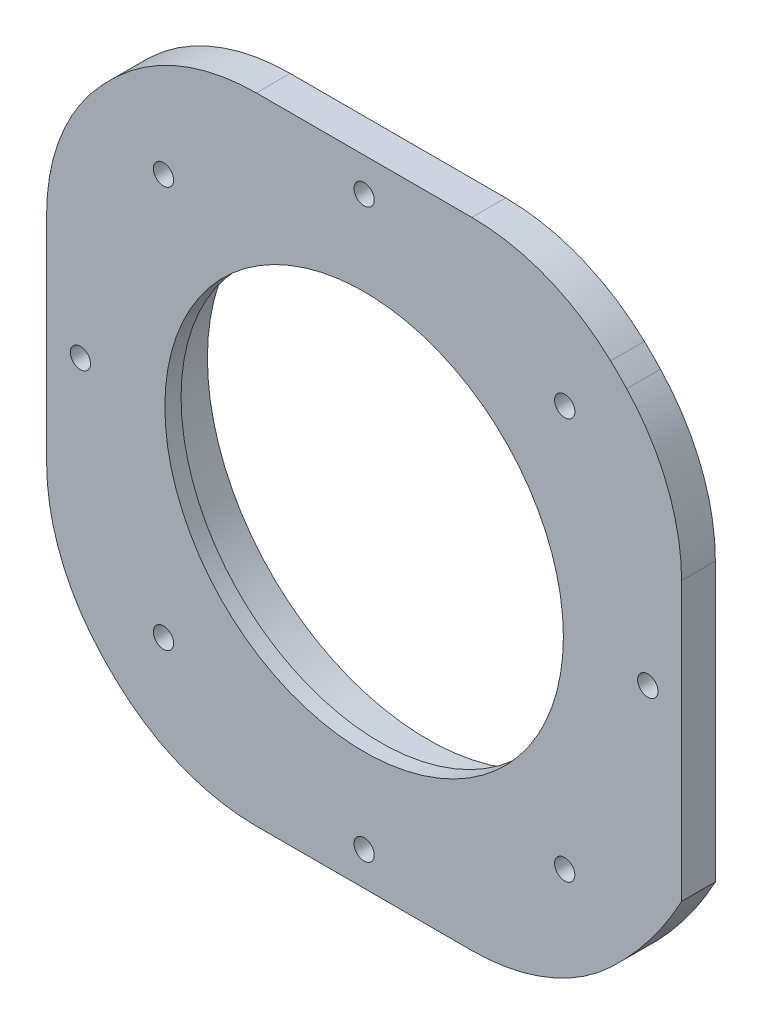
SolidWorks part; units mm, degrees
ref_plane "Front Plane" through (0, 0, 0) normal (0, 0, 1) x (1, 0, 0)
ref_plane "Top Plane" through (0, 0, 0) normal (0, 1, 0) x (1, 0, 0)
ref_plane "Right Plane" through (0, 0, 0) normal (1, 0, 0) x (0, 0, -1)
sketch "Sketch1" plane through (0, 0, 0) normal (0, 0, 1) x (1, 0, 0)
  line L4 (-47, 15.9577) -> (-47, -15.9577)
  line L5 (-15.9577, -47) -> (15.9577, -47)
  line L6 (47, -25.1719) -> (47, 15.9577)
  line L7 (15.9577, 47) -> (-15.9577, 47)
  circle A1 centre (0, 0) radius 36
  arc A2 (32.6244, 15.22) -> (34.2676, 11.0331) centre (33.5115, 13.1523) ccw
  arc A4 (26.6888, 24.1601) -> (29.4931, 20.6435) centre (28.1459, 22.4456) ccw
  arc A6 (18.3818, 30.9534) -> (22.098, 28.4196) centre (20.2795, 29.7446) ccw
  arc A8 (8.4415, 34.9963) -> (12.7395, 33.6706) centre (10.6112, 34.4006) ccw
  arc A10 (-2.2489, 35.9297) -> (2.2489, 35.9297) centre (0, 36) ccw
  arc A12 (-12.7395, 33.6706) -> (-8.4415, 34.9963) centre (-10.6112, 34.4006) ccw
  arc A14 (-22.098, 28.4196) -> (-18.3818, 30.9534) centre (-20.2795, 29.7446) ccw
  arc A16 (-29.4931, 20.6435) -> (-26.6888, 24.1601) centre (-28.1459, 22.4456) ccw
  arc A18 (-34.2676, 11.0331) -> (-32.6244, 15.22) centre (-33.5115, 13.1523) ccw
  arc A20 (-35.9973, 0.4424) -> (-35.6612, 4.9276) centre (-35.8993, 2.6903) ccw
  arc A22 (-34.5284, -10.1876) -> (-35.5293, -5.8026) centre (-35.0974, -8.0108) ccw
  arc A24 (-29.9916, -19.9124) -> (-32.2405, -16.0172) centre (-31.1769, -18) ccw
  arc A26 (-22.7898, -27.868) -> (-26.087, -24.8087) centre (-24.4862, -26.3899) ccw
  arc A28 (-13.5631, -33.3473) -> (-17.6155, -31.3958) centre (-15.6198, -32.4349) ccw
  arc A30 (-3.1313, -35.8636) -> (-7.5788, -35.1932) centre (-5.3655, -35.5979) ccw
  arc A32 (7.5788, -35.1932) -> (3.1313, -35.8636) centre (5.3655, -35.5979) ccw
  arc A34 (17.6155, -31.3958) -> (13.5631, -33.3473) centre (15.6198, -32.4349) ccw
  arc A36 (26.087, -24.8087) -> (22.7898, -27.868) centre (24.4862, -26.3899) ccw
  arc A38 (32.2405, -16.0172) -> (29.9916, -19.9124) centre (31.1769, -18) ccw
  arc A40 (35.5293, -5.8026) -> (34.5284, -10.1876) centre (35.0974, -8.0108) ccw
  arc A42 (35.6612, 4.9276) -> (35.9973, 0.4424) centre (35.8993, 2.6903) ccw
  arc A46 (32.7, 0) -> (-32.7, 0) centre (0, 0) ccw
  arc A47 (-32.7, 0) -> (32.7, 0) centre (0, 0) ccw
  arc A225 (-36.4898, 38.8731) -> (-38.8731, 36.4898) centre (0, 0) ccw
  arc A226 (-38.8731, 36.4898) -> (-47, 15.9577) centre (-17, 15.9577) ccw
  arc A227 (-47, -15.9577) -> (-38.8731, -36.4898) centre (-17, -15.9577) ccw
  arc A228 (-38.8731, -36.4898) -> (-36.4898, -38.8731) centre (0, 0) ccw
  arc A229 (-36.4898, -38.8731) -> (-15.9577, -47) centre (-15.9577, -17) ccw
  arc A230 (15.9577, -47) -> (36.4898, -38.8731) centre (15.9577, -17) ccw
  arc A231 (36.4898, -38.8731) -> (47, -25.1719) centre (0, 0) ccw
  arc A232 (47, 15.9577) -> (38.8731, 36.4898) centre (17, 15.9577) ccw
  arc A233 (38.8731, 36.4898) -> (36.4898, 38.8731) centre (0, 0) ccw
  arc A234 (36.4898, 38.8731) -> (15.9577, 47) centre (15.9577, 17) ccw
  arc A235 (-15.9577, 47) -> (-36.4898, 38.8731) centre (-15.9577, 17) ccw
extrude "Boss-Extrude1" add sketch "Sketch1" along normal blind 5 contours L7 A235 A225 A226 L4 A227 A228 A229 L5 A230 A231 L6 A232 A233 A234 A1 | A42 A1 A2 A4 A6 A8 A10 A12 A14 A16 A18 A20 A22 A24 A26 A28 A30 A32 A34 A36 A38 A40 A47 A46 | A46 A47 region at (-43.6583, 26.5094, 0) region at (34.8677, -2.8285, 0) region at (0, 0, 0)
extrude "Boss-Extrude2" add sketch "Sketch1<4>" against normal offset from surface (4.4 mm away) 0.2 contours A42 A1 A2 A4 A6 A8 A10 A12 A14 A16 A18 A20 A22 A24 A26 A28 A30 A32 A34 A36 A38 A40 A47 A46 region at (34.8677, -2.8285, 0)
sketch "Sketch1<4>" plane through (0, 0, 0) normal (0, 0, 1) x (1, 0, 0) same geometry as "Sketch1"
sketch "Sketch2" plane through (0, 0, 5) normal (0, 0, 1) x (1, 0, 0)
  line L4 (15.9577, 47) -> (-15.9577, 47)
  line L5 (-47, 15.9577) -> (-47, -15.9577)
  line L6 (-15.9577, -47) -> (15.9577, -47)
  line L7 (47, -25.1719) -> (47, 15.9577)
  line L8 (15.9577, 47) -> (-15.9577, 47)
  line L9 (-47, 15.9577) -> (-47, -15.9577)
  line L10 (-15.9577, -47) -> (15.9577, -47)
  line L11 (47, -25.1719) -> (47, 15.9577)
  arc A11 (-15.9577, 47) -> (-36.4898, 38.8731) centre (-15.9577, 17) ccw
  arc A12 (-36.4898, 38.8731) -> (-38.8731, 36.4898) centre (0, 0) ccw
  arc A13 (-38.8731, 36.4898) -> (-47, 15.9577) centre (-17, 15.9577) ccw
  arc A14 (-47, -15.9577) -> (-38.8731, -36.4898) centre (-17, -15.9577) ccw
  arc A15 (-38.8731, -36.4898) -> (-36.4898, -38.8731) centre (0, 0) ccw
  arc A16 (-36.4898, -38.8731) -> (-15.9577, -47) centre (-15.9577, -17) ccw
  arc A17 (15.9577, -47) -> (36.4898, -38.8731) centre (15.9577, -17) ccw
  arc A18 (36.4898, -38.8731) -> (47, -25.1719) centre (0, 0) ccw
  arc A19 (47, 15.9577) -> (38.8731, 36.4898) centre (17, 15.9577) ccw
  arc A20 (38.8731, 36.4898) -> (36.4898, 38.8731) centre (0, 0) ccw
  arc A21 (36.4898, 38.8731) -> (15.9577, 47) centre (15.9577, 17) ccw
  arc A22 (-15.9577, 47) -> (-36.4898, 38.8731) centre (-15.9577, 17) ccw
  arc A23 (-36.4898, 38.8731) -> (-38.8731, 36.4898) centre (0, 0) ccw
  arc A24 (-38.8731, 36.4898) -> (-47, 15.9577) centre (-17, 15.9577) ccw
  arc A25 (-47, -15.9577) -> (-38.8731, -36.4898) centre (-17, -15.9577) ccw
  arc A26 (-38.8731, -36.4898) -> (-36.4898, -38.8731) centre (0, 0) ccw
  arc A27 (-36.4898, -38.8731) -> (-15.9577, -47) centre (-15.9577, -17) ccw
  arc A28 (15.9577, -47) -> (36.4898, -38.8731) centre (15.9577, -17) ccw
  arc A29 (36.4898, -38.8731) -> (47, -25.1719) centre (0, 0) ccw
  arc A30 (47, 15.9577) -> (38.8731, 36.4898) centre (17, 15.9577) ccw
  arc A31 (38.8731, 36.4898) -> (36.4898, 38.8731) centre (0, 0) ccw
  arc A32 (36.4898, 38.8731) -> (15.9577, 47) centre (15.9577, 17) ccw
  dimension "D1" = 0
extrude "Boss-Extrude3" add sketch "Sketch2" against normal up to surface (5 mm away) up to face at (0, 0, 0)
sketch "Sketch3" plane through (0, 0, 0) normal (0, 0, -1) x (-1, 0, 0)
  circle A0 centre (0, 0) radius 32.6
  circle A1 centre (0, 0) radius 32.7
  circle A2 centre (0, 0) radius 32.7
  dimension "D1" = 0
  dimension "D2" = 0.1
extrude "Boss-Extrude4" add sketch "Sketch3" along normal up to surface (4.4 mm away) up to face at (0, 0, -4.4)
sketch "Sketch4" plane through (0, 0, 5) normal (0, 0, 1) x (1, 0, 0)
  line L4 (15.9577, 47) -> (-15.9577, 47)
  line L5 (-47, 15.9577) -> (-47, -15.9577)
  line L6 (-15.9577, -47) -> (15.9577, -47)
  line L7 (47, -25.1719) -> (47, 15.9577)
  line L8 (15.9577, 47) -> (-15.9577, 47)
  line L9 (-47, 15.9577) -> (-47, -15.9577)
  line L10 (-15.9577, -47) -> (15.9577, -47)
  line L11 (47, -25.1719) -> (47, 15.9577)
  circle A0 centre (0, 0) radius 32.6
  arc A11 (-15.9577, 47) -> (-36.4898, 38.8731) centre (-15.9577, 17) ccw
  arc A12 (-36.4898, 38.8731) -> (-38.8731, 36.4898) centre (0, 0) ccw
  arc A13 (-38.8731, 36.4898) -> (-47, 15.9577) centre (-17, 15.9577) ccw
  arc A14 (-47, -15.9577) -> (-38.8731, -36.4898) centre (-17, -15.9577) ccw
  arc A15 (-38.8731, -36.4898) -> (-36.4898, -38.8731) centre (0, 0) ccw
  arc A16 (-36.4898, -38.8731) -> (-15.9577, -47) centre (-15.9577, -17) ccw
  arc A17 (15.9577, -47) -> (36.4898, -38.8731) centre (15.9577, -17) ccw
  arc A18 (36.4898, -38.8731) -> (47, -25.1719) centre (0, 0) ccw
  arc A19 (47, 15.9577) -> (38.8731, 36.4898) centre (17, 15.9577) ccw
  arc A20 (38.8731, 36.4898) -> (36.4898, 38.8731) centre (0, 0) ccw
  arc A21 (36.4898, 38.8731) -> (15.9577, 47) centre (15.9577, 17) ccw
  arc A22 (-15.9577, 47) -> (-36.4898, 38.8731) centre (-15.9577, 17) ccw
  arc A23 (-36.4898, 38.8731) -> (-38.8731, 36.4898) centre (0, 0) ccw
  arc A24 (-38.8731, 36.4898) -> (-47, 15.9577) centre (-17, 15.9577) ccw
  arc A25 (-47, -15.9577) -> (-38.8731, -36.4898) centre (-17, -15.9577) ccw
  arc A26 (-38.8731, -36.4898) -> (-36.4898, -38.8731) centre (0, 0) ccw
  arc A27 (-36.4898, -38.8731) -> (-15.9577, -47) centre (-15.9577, -17) ccw
  arc A28 (15.9577, -47) -> (36.4898, -38.8731) centre (15.9577, -17) ccw
  arc A29 (36.4898, -38.8731) -> (47, -25.1719) centre (0, 0) ccw
  arc A30 (47, 15.9577) -> (38.8731, 36.4898) centre (17, 15.9577) ccw
  arc A31 (38.8731, 36.4898) -> (36.4898, 38.8731) centre (0, 0) ccw
  arc A32 (36.4898, 38.8731) -> (15.9577, 47) centre (15.9577, 17) ccw
  dimension "D2" = 65.2
  dimension "D1" = 0
extrude "Cut-Extrude1" cut sketch "Sketch4" against normal through all both contours A0 region at (0, 0, 5)
sketch "Sketch5" plane through (0, 0, 5) normal (0, 0, 1) x (1, 0, 0)
  line L4 (15.9577, 47) -> (-15.9577, 47)
  line L5 (-47, 15.9577) -> (-47, -15.9577)
  line L6 (-15.9577, -47) -> (15.9577, -47)
  line L7 (47, -25.1719) -> (47, 15.9577)
  line L8 (15.9577, 47) -> (-15.9577, 47)
  line L9 (-47, 15.9577) -> (-47, -15.9577)
  line L10 (-15.9577, -47) -> (15.9577, -47)
  line L11 (47, -25.1719) -> (47, 15.9577)
  circle A0 centre (0, 0) radius 29.5
  arc A12 (-15.9577, 47) -> (-36.4898, 38.8731) centre (-15.9577, 17) ccw
  arc A13 (-36.4898, 38.8731) -> (-38.8731, 36.4898) centre (0, 0) ccw
  arc A14 (-38.8731, 36.4898) -> (-47, 15.9577) centre (-17, 15.9577) ccw
  arc A15 (-47, -15.9577) -> (-38.8731, -36.4898) centre (-17, -15.9577) ccw
  arc A16 (-38.8731, -36.4898) -> (-36.4898, -38.8731) centre (0, 0) ccw
  arc A17 (-36.4898, -38.8731) -> (-15.9577, -47) centre (-15.9577, -17) ccw
  arc A18 (15.9577, -47) -> (36.4898, -38.8731) centre (15.9577, -17) ccw
  arc A19 (36.4898, -38.8731) -> (47, -25.1719) centre (0, 0) ccw
  arc A20 (47, 15.9577) -> (38.8731, 36.4898) centre (17, 15.9577) ccw
  arc A21 (38.8731, 36.4898) -> (36.4898, 38.8731) centre (0, 0) ccw
  arc A22 (36.4898, 38.8731) -> (15.9577, 47) centre (15.9577, 17) ccw
  arc A23 (-15.9577, 47) -> (-36.4898, 38.8731) centre (-15.9577, 17) ccw
  arc A24 (-36.4898, 38.8731) -> (-38.8731, 36.4898) centre (0, 0) ccw
  arc A25 (-38.8731, 36.4898) -> (-47, 15.9577) centre (-17, 15.9577) ccw
  arc A26 (-47, -15.9577) -> (-38.8731, -36.4898) centre (-17, -15.9577) ccw
  arc A27 (-38.8731, -36.4898) -> (-36.4898, -38.8731) centre (0, 0) ccw
  arc A28 (-36.4898, -38.8731) -> (-15.9577, -47) centre (-15.9577, -17) ccw
  arc A29 (15.9577, -47) -> (36.4898, -38.8731) centre (15.9577, -17) ccw
  arc A30 (36.4898, -38.8731) -> (47, -25.1719) centre (0, 0) ccw
  arc A31 (47, 15.9577) -> (38.8731, 36.4898) centre (17, 15.9577) ccw
  arc A32 (38.8731, 36.4898) -> (36.4898, 38.8731) centre (0, 0) ccw
  arc A33 (36.4898, 38.8731) -> (15.9577, 47) centre (15.9577, 17) ccw
  dimension "D1" = 59
  dimension "D2" = 0
extrude "Boss-Extrude5" add sketch "Sketch5" against normal offset from surface (2.4 mm away) 7 up to face at (0, 0, -4.4)
sketch "Sketch6" plane through (0, 0, 5) normal (0, 0, 1) x (1, 0, 0)
  circle A0 centre (42, 0) radius 1.5
  circle A1 centre (29.6985, -29.6985) radius 1.5
  circle A2 centre (0, -42) radius 1.5
  circle A3 centre (-29.6985, -29.6985) radius 1.5
  circle A4 centre (-42, 0) radius 1.5
  circle A5 centre (-29.6985, 29.6985) radius 1.5
  circle A6 centre (0, 42) radius 1.5
  circle A7 centre (29.6985, 29.6985) radius 1.5
  point P45 (0, 0)
  dimension "D2" = 3
  dimension "D4" = 8
extrude "Cut-Extrude3" cut sketch "Sketch6" against normal through all both and the other way through all
